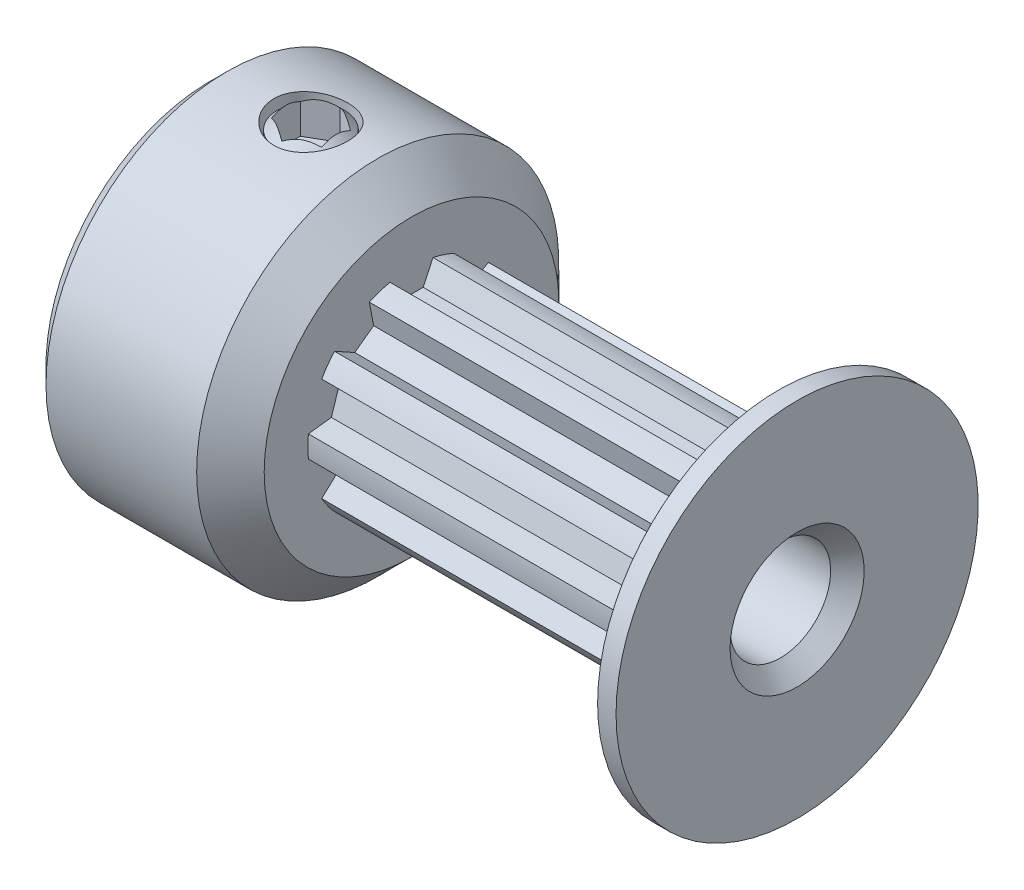
SolidWorks part; units mm, degrees
ref_plane "Front Plane" through (0, 0, 0) normal (0, 0, 1) x (1, 0, 0)
ref_plane "Top Plane" through (0, 0, 0) normal (0, 1, 0) x (1, 0, 0)
ref_plane "Right Plane" through (0, 0, 0) normal (1, 0, 0) x (0, 0, -1)
sketch "Sketch2" plane through (0, 0, 0) normal (1, 0, 0) x (0, 0, -1)
  line L3 (0, 0) -> (0, 2.4245) construction
  line L6 (0, -2.9325) -> (0, -3.25) construction
  line L7 (-0.5715, 2.8763) -> (-0.3491, 2.3992)
  line L8 (0.5715, 2.8763) -> (0.3491, 2.3992)
  line L9 (-0.5715, 2.8763) -> (-0.6405, 3.0242)
  line L10 (0.5715, 2.8763) -> (0.6405, 3.0242)
  line L12 (-0.3491, 2.3992) -> (0.3491, 2.3992)
  line L14 (0, 2.9325) -> (0, 3.25) construction
  line L15 (0, 0) -> (0, -1.143) construction
  circle A0 centre (0, 0) radius 3.25 construction
  circle A1 centre (0, 0) radius 2.4245 construction
  circle A2 centre (0, 0) radius 2.9325 construction
  arc A7 (0.6405, 3.0242) -> (-0.6405, 3.0242) centre (0, 0) ccw
  point P5 (0, 3.0912)
  dimension "D3" = 0.3175
  dimension "D1" = 50
sketch "Sketch1" plane through (0, 0, 0) normal (0, 0, 1) x (1, 0, 0)
  line L0 (-8.75, 0) -> (8.75, 0) construction
  line L1 (-8.75, 1.5) -> (8.75, 1.5)
  line L2 (-8.75, 1.5) -> (-8.75, 5.4)
  line L3 (-8.75, 5.4) -> (-3.757, 5.4)
  line L4 (-3.757, 5.4) -> (-2.75, 4.393)
  line L5 (-2.75, 4.393) -> (-2.75, 3.25)
  line L6 (-2.75, 3.25) -> (7.65, 3.25)
  line L7 (7.65, 3.25) -> (7.65, 3.8215)
  line L8 (7.65, 3.25) -> (8.75, 3.25) construction
  line L9 (8.2, 5.4) -> (8.75, 5.4)
  line L10 (8.75, 5.4) -> (8.75, 1.5)
  line L11 (8.2, 3.25) -> (8.2, 5.4) construction
  line L12 (-6.2535, 5.4) -> (-6.2535, 1.5) construction
  arc A0 (7.65, 3.8215) -> (8.2, 5.4) centre (10.1901, 3.8215) cw
  dimension "Bore Size" = 3
  dimension "Overall Width" = 17.5
  dimension "Inside Width" = 10.4
  dimension "Outside Width" = 11.5
  dimension "Hub Dia" = 10.8
  dimension "OD" = 10.8
  dimension "D1" = 45
  dimension "D2" = 6.5
  dimension "D3" = 1.143
  dimension "D4" = 0.5715
revolve "Revolve1" add sketch "Sketch1" angle 360 mid plane about L0
sketch "Sketch4" plane through (-2.75, 0, 0) normal (1, 0, 0) x (0, 0, -1)
  circle A0 centre (0, 0) radius 3.0912
  circle A1 centre (0, 0) radius 3.25 construction
  circle A2 centre (0, 0) radius 3.25
extrude "Cut-Extrude2" cut sketch "Sketch4" along normal up to surface (10.4 mm away) up to face at (7.65, 0, 3.25)
sketch "Sketch3" plane through (-2.75, 0, 0) normal (1, 0, 0) x (0, 0, -1)
  line L2 (-0.5715, 2.8763) -> (-0.3491, 2.3992) construction
  line L3 (-0.3491, 2.3992) -> (0.3491, 2.3992) construction
  line L4 (0.5715, 2.8763) -> (0.3491, 2.3992) construction
  line L5 (-0.6405, 3.0242) -> (-0.3491, 2.3992)
  line L6 (-0.3491, 2.3992) -> (0.3491, 2.3992)
  line L7 (0.6405, 3.0242) -> (0.3491, 2.3992)
  arc A1 (0.6405, 3.0242) -> (-0.6405, 3.0242) centre (0, 0) ccw construction
  arc A2 (0.6405, 3.0242) -> (-0.6405, 3.0242) centre (0, 0) ccw
extrude "Cut-Extrude1" cut sketch "Sketch3" along normal up to surface (10.4 mm away)
pattern_circular "CirPattern1" count 10 over 360 of "Cut-Extrude1"
sketch "Sketch5" plane through (0, 0, 0) normal (0, 0, 1) x (1, 0, 0)
  line L1 (7.65, 3.8215) -> (7.65, -3.8215) construction
  point P0 (7.65, 0)
sketch "Sketch6" plane through (0, 0, 0) normal (0, 1, 0) x (1, 0, 0)
  line L0 (-8.75, 0) -> (-6.75, 0) construction
  line L1 (-8.75, 5.4) -> (-8.75, -5.4) construction
  line L2 (-2.75, 0) -> (-4.75, 0) construction
  line L3 (-2.75, -0.3491) -> (-2.75, 0.3491) construction
  circle A0 centre (-5.75, 0) radius 1 construction
  circle A1 centre (-5.75, 0) radius 1.1
  dimension "D1" = 0.1
  dimension "SS Dia" = 2
extrude "Cut-Extrude3" cut sketch "Sketch6" along normal through all
sketch "Sketch7" plane through (0, 0, 0) normal (0, 0, 1) x (1, 0, 0)
  line L0 (-6.496, 5.4) -> (-5.75, 5.4)
  line L1 (-6.75, 5.146) -> (-6.75, 2.135)
  line L2 (-6.75, 2.135) -> (-6.496, 1.881)
  line L3 (-6.496, 1.881) -> (-5.75, 1.881)
  line L4 (-5.75, 1.881) -> (-5.75, 5.4) construction
  line L6 (-6.75, 5.146) -> (-6.496, 5.4)
  line L7 (-8.75, 5.4) -> (-3.757, 5.4) construction
  line L8 (-5.75, 5.4) -> (-5.75, 1.881)
  point P0 (-6.75, 5.4)
  point P4 (-6.75, 1.881)
  dimension "D2" = 0.381
revolve "Revolve2" add sketch "Sketch7" angle 360 mid plane about L4
sketch "Sketch8" plane through (0, 5.4, 0) normal (0, 1, 0) x (1, 0, 0)
  line L1 (-5.75, 0.866) -> (-6.5, 0.433)
  line L2 (-6.5, 0.433) -> (-6.5, -0.433)
  line L3 (-6.5, -0.433) -> (-5.75, -0.866)
  line L4 (-5.75, -0.866) -> (-5, -0.433)
  line L5 (-5, -0.433) -> (-5, 0.433)
  line L6 (-5, 0.433) -> (-5.75, 0.866)
  circle A0 centre (-5.75, 0) radius 0.75 construction
  dimension "D1" = 1.5
extrude "Cut-Extrude4" cut sketch "Sketch8" against normal blind 1.016
pattern_circular "CirPattern2" [suppressed] count 2 over 90 reverse direction yes of bodies 105
pattern_circular "CirPattern3" [suppressed] count 2 over 90 reverse direction yes of bodies 107
chamfer "Chamfer1" distance 0.5 angle 45 3 edges at (-8.75, 0, 5.4) (-8.75, 0, 1.5) (8.75, 0, 1.5)
ref_axis "Center Axis 1" through (8.25, 0, 0) along (-1, 0, 0)
ref_plane "Contact Plane 1" through (8.75, 0, 0) normal (1, 0, 0) x (0, 0, -1)
ref_plane "Contact Plane 2" through (-8.75, 0, 0) normal (-1, 0, 0) x (0, 0, 1)
equation "\"D3@Sketch2\" = (\"hs@Sketch2\"-\"ht@Sketch2\")/2"
equation "\"D2@Sketch1\" = \"PD@Sketch2\""
equation "\"D3@Sketch1\" = \"hs@Sketch2\""
equation "\"D4@Sketch1\" = \"D3@Sketch1\"/2"
